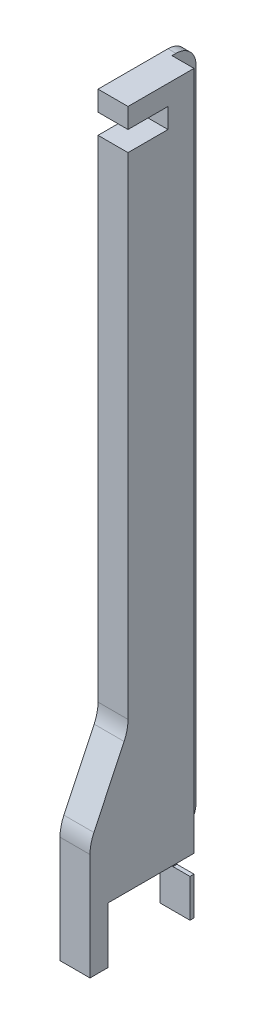
SolidWorks part; units mm, degrees
ref_plane "정면" through (0, 0, 0) normal (0, 0, 1) x (1, 0, 0)
ref_plane "윗면" through (0, 0, 0) normal (0, 1, 0) x (1, 0, 0)
ref_plane "우측면" through (0, 0, 0) normal (1, 0, 0) x (0, 0, -1)
sketch "스케치1" plane through (0, 0, 0) normal (0, 0, 1) x (1, 0, 0)
  line L0 (-318.5049, 0) -> (318.5049, 0) construction
  line L1 (0, 0) -> (0, -258.8265) construction
  line L2 (-168, 0) -> (168, 0)
  line L3 (-168, -20) -> (168, -20)
  line L4 (168, -20) -> (168, 0) construction
  line L5 (168, -20) -> (168, -340)
  line L6 (172, -340) -> (172, 0)
  line L7 (168, 0) -> (183, 0)
  line L8 (183, 0) -> (183, -340)
  line L9 (183, -340) -> (168, -340)
  line L10 (-168, -20) -> (-168, 0) construction
  line L11 (-183, -340) -> (-168, -340)
  line L12 (-183, 0) -> (-183, -340)
  line L13 (-168, 0) -> (-183, 0)
  line L14 (-172, -340) -> (-172, 0)
  line L15 (-168, -20) -> (-168, -340)
  line L16 (168, -20) -> (168, 0)
  line L17 (-168, -20) -> (-168, 0)
  point P14 (0, -20)
  dimension "D1" = 168
  dimension "D2" = 20
  dimension "D3" = 4
  dimension "D4" = 340
  dimension "D5" = 15
extrude "보스-돌출1" add sketch "스케치1" along normal blind 26 contours L3 L5 L9 L8 L7 L2 L13 L12 L11 L15
extrude "보스-돌출2" add sketch "스케치1<4>" against normal blind 19 contours L16 L5 L9 L6 L7 | L15 L17 L13 L14 L11 region at (-170, -170, 0) region at (170, -170, 0)
sketch "스케치1<4>" plane through (0, 0, 0) normal (0, 0, 1) x (1, 0, 0) same geometry as "스케치1"
fillet "필렛1" radius 10 4 edges at (-170, 0, -19) (170, 0, -19) (170, -340, -19) (-170, -340, -19)
sketch "스케치2" plane through (172, 0, 0) normal (1, 0, 0) x (0, 0, -1)
  line L0 (14, -340) -> (14, 0)
  line L1 (12, 0) -> (12, -340)
  line L4 (19, -330) -> (19, -10)
  line L5 (9, 0) -> (0, 0)
  line L6 (0, 0) -> (0, -340)
  line L7 (0, -340) -> (9, -340)
  line L8 (19, -330) -> (19, -10)
  line L9 (9, 0) -> (0, 0)
  line L10 (0, 0) -> (0, -340)
  line L11 (0, -340) -> (9, -340)
  arc A2 (19, -10) -> (9, 0) centre (9, -10) ccw
  arc A3 (9, -340) -> (19, -330) centre (9, -330) ccw
  arc A4 (19, -10) -> (9, 0) centre (9, -10) ccw
  arc A5 (9, -340) -> (19, -330) centre (9, -330) ccw
  dimension "D2" = 5
  dimension "D3" = 2
  dimension "D1" = 0
sketch "스케치3" plane through (168, 0, 0) normal (-1, 0, 0) x (0, 0, 1)
  line L0 (-12, 0) -> (-12, -340) construction
  line L1 (-14, -340) -> (-14, 0) construction
  line L2 (-12, 0) -> (-12, -340)
  line L3 (-14, -340) -> (-14, 0)
  line L4 (-19, -10) -> (-19, -330)
  line L5 (0, 0) -> (-9, 0)
  line L6 (0, -340) -> (0, 0)
  line L7 (-9, -340) -> (0, -340)
  line L8 (-19, -10) -> (-19, -330)
  line L9 (0, 0) -> (-9, 0)
  line L10 (0, -340) -> (0, 0)
  line L11 (-9, -340) -> (0, -340)
  arc A2 (-9, 0) -> (-19, -10) centre (-9, -10) ccw
  arc A3 (-19, -330) -> (-9, -340) centre (-9, -330) ccw
  arc A4 (-9, 0) -> (-19, -10) centre (-9, -10) ccw
  arc A5 (-19, -330) -> (-9, -340) centre (-9, -330) ccw
  dimension "D1" = 0
sketch "스케치5" plane through (0, 0, 0) normal (0, 1, 0) x (1, 0, 0)
  line L0 (-7, 0) -> (-7, -26)
  line L1 (7, 0) -> (7, -26)
  line L2 (-168, 0) -> (-168, -6)
  line L3 (-168, -6) -> (-7, -6)
  line L4 (7, -6) -> (168, -6)
  line L5 (168, -6) -> (168, 0)
  line L12 (-168, 0) -> (-168, 9)
  line L13 (-168, 9) -> (-172, 9)
  line L14 (-172, 9) -> (-172, 0)
  line L15 (-172, 0) -> (-183, 0)
  line L16 (-183, 0) -> (-183, -26)
  line L17 (-183, -26) -> (183, -26)
  line L18 (183, -26) -> (183, 0)
  line L19 (183, 0) -> (172, 0)
  line L20 (172, 0) -> (172, 9)
  line L21 (172, 9) -> (168, 9)
  line L22 (168, 9) -> (168, 0)
  line L23 (168, 0) -> (-168, 0)
  line L24 (-168, 0) -> (-168, 9)
  line L25 (-168, 9) -> (-172, 9)
  line L26 (-172, 9) -> (-172, 0)
  line L27 (-172, 0) -> (-183, 0)
  line L28 (-183, 0) -> (-183, -26)
  line L29 (-183, -26) -> (183, -26)
  line L30 (183, -26) -> (183, 0)
  line L31 (183, 0) -> (172, 0)
  line L32 (172, 0) -> (172, 9)
  line L33 (172, 9) -> (168, 9)
  line L34 (168, 9) -> (168, 0)
  line L35 (168, 0) -> (-168, 0)
  line M27 (168, 0) -> (-168, 0)
  dimension "D2" = 7
  dimension "D3" = 7
  dimension "D4" = 6
  dimension "D1" = 0
extrude "컷-돌출1" cut sketch "스케치5" against normal blind 52 contours L2 L3 L0 M27 | L4 L5 L1 M27 region at (-87.5, 0, 3) region at (87.5, 0, 3)
extrude "보스-돌출4" add sketch "스케치1<5>" against normal blind 7 contours L9 L8 L7 L6 | L11 L14 L13 L12 region at (-177.5, -170, 0) region at (177.5, -170, 0)
sketch "스케치1<5>" plane through (0, 0, 0) normal (0, 0, 1) x (1, 0, 0) same geometry as "스케치1"
sketch "스케치6" plane through (0, -340, 0) normal (0, -1, 0) x (1, 0, 0)
  line L0 (-172, -7) -> (-126.7636, -7) construction
  line L1 (-172, -7) -> (-168, -7)
  line L2 (-168, -7) -> (-168, -5)
  line L3 (-168, -5) -> (-174.5, -5)
  line L4 (-174.5, -5) -> (-174.5, -7)
  line L5 (-181.1, -7) -> (-181.1, -5)
  line L6 (-172, -7) -> (-172, -9)
  line L7 (-172, -9) -> (-168, -9)
  line L8 (-168, -9) -> (-168, 26)
  line L9 (-168, 26) -> (-183, 26)
  line L10 (-183, 26) -> (-183, -7)
  line L11 (-183, -7) -> (-172, -7)
  line L12 (-172, -7) -> (-172, -9)
  line L13 (-172, -9) -> (-168, -9)
  line L14 (-168, -9) -> (-168, 26)
  line L15 (-168, 26) -> (-183, 26)
  line L16 (-183, 26) -> (-183, -7)
  line L17 (-183, -7) -> (-172, -7)
  line L18 (-181.1, -5) -> (-183, -5)
  line L19 (-181.1, -5) -> (-174.5, -5)
  line L20 (-168, 26) -> (-168, 36)
  line L21 (-168, 36) -> (-183, 36)
  line L22 (-183, 36) -> (-183, 26)
  line L23 (-168, 36) -> (-168, 45)
  line L24 (-168, 45) -> (-183, 45)
  line L25 (-183, 45) -> (-183, 36)
  line M14 (-168, -9) -> (-168, 26)
  line M15 (-168, 26) -> (-183, 26)
  line M17 (-183, -7) -> (-172, -7)
  dimension "D2" = 6.5
  dimension "D3" = 2
  dimension "D4" = 6.6
  dimension "D5" = 41
  dimension "D6" = 9
  dimension "D1" = 0
extrude "보스-돌출5" add sketch "스케치6" along normal blind 28 contours L5 L18 L16 M17 | L19 L5 L4 M17 | L3 L4 L1 M17 M14 region at (-171.25, -340, -6) region at (-177.8, -340, -6) region at (-182.05, -340, -6)
extrude "컷-돌출2" cut sketch "스케치6<3>" along normal blind 5 contours L19 L5 L4 M17 region at (-177.8, -340, -6)
sketch "스케치6<3>" plane through (0, -340, 0) normal (0, -1, 0) x (1, 0, 0) same geometry as "스케치6"
fillet "필렛2" radius 20 1 edges at (-170, -340, -7)
extrude "보스-돌출6" add sketch "스케치6<4>" against normal blind 30 contours L21 L22 L20 M15 | L24 L25 L21 L23 region at (-175.5, -340, 31) region at (-175.5, -340, 40.5)
sketch "스케치6<4>" plane through (0, -340, 0) normal (0, -1, 0) x (1, 0, 0) same geometry as "스케치6"
extrude "보스-돌출7" add sketch "스케치6<5>" along normal blind 28 contours L24 L25 L21 L23 region at (-175.5, -340, 40.5)
sketch "스케치6<5>" plane through (0, -340, 0) normal (0, -1, 0) x (1, 0, 0) same geometry as "스케치6"
sketch "스케치9" plane through (-183, 0, 0) normal (-1, 0, 0) x (0, 0, 1)
  line L0 (45, -310) -> (26, -270)
  line L1 (26, 0) -> (26, -310) construction
  line L12 (26, 0) -> (-7, 0)
  line L13 (-7, 0) -> (-7, -368)
  line L14 (-7, -368) -> (-5, -368)
  line L15 (-5, -368) -> (-5, -340)
  line L16 (-5, -340) -> (36, -340)
  line L17 (36, -340) -> (36, -368)
  line L18 (36, -368) -> (45, -368)
  line L19 (45, -368) -> (45, -310)
  line L20 (45, -310) -> (26, -310)
  line L21 (26, -310) -> (26, 0)
  line L22 (26, 0) -> (-7, 0)
  line L23 (-7, 0) -> (-7, -368)
  line L24 (-7, -368) -> (-5, -368)
  line L25 (-5, -368) -> (-5, -340)
  line L26 (-5, -340) -> (36, -340)
  line L27 (36, -340) -> (36, -368)
  line L28 (36, -368) -> (45, -368)
  line L29 (45, -368) -> (45, -310)
  line L30 (45, -310) -> (26, -310)
  line L31 (26, -310) -> (26, 0)
  line M19 (45, -310) -> (26, -310)
  line M20 (26, -310) -> (26, 0)
  dimension "D2" = 40
  dimension "D1" = 0
extrude "보스-돌출8" add sketch "스케치9" against normal blind 15 contours L0 M19 M20 region at (-183, -296.6667, 32.3333)
fillet "필렛3" radius 20 2 edges at (-175.5, -270, 26) (-175.5, -310, 45)
mirror "대칭 복사2" about plane through (0, 0, 0) normal (1, 0, 0) of "보스-돌출5", "컷-돌출2", "필렛3", "보스-돌출6", "보스-돌출7", "보스-돌출8"
fillet "필렛4" radius 20 1 edges at (170, -340, -7)
sketch "스케치10" plane through (183, 0, 0) normal (1, 0, 0) x (0, 0, -1)
  line L0 (-27.9344, -274.0725) -> (-43.0656, -305.9275) construction
  line L1 (-45, -314.5086) -> (-45, -368) construction
  line L2 (-45, -368) -> (-36, -368) construction
  line L3 (-36, -368) -> (-36, -340) construction
  line L4 (-36, -340) -> (5, -340) construction
  line L5 (5, -340) -> (5, -368) construction
  line L6 (5, -368) -> (7, -368) construction
  line L7 (7, -368) -> (7, -354) construction
  line L8 (19, -330) -> (19, -10) construction
  line L9 (9, 0) -> (-6, 0) construction
  line L10 (-6, 0) -> (-6, -20) construction
  line L11 (-6, -20) -> (-26, -20) construction
  line L12 (-26, -20) -> (-26, -265.4914) construction
  line L13 (-27.9344, -274.0725) -> (-43.0656, -305.9275) construction
  line L14 (-45, -314.5086) -> (-45, -368) construction
  line L15 (-45, -368) -> (-36, -368) construction
  line L16 (-36, -368) -> (-36, -340) construction
  line L17 (-36, -340) -> (5, -340) construction
  line L18 (5, -340) -> (5, -368) construction
  line L19 (5, -368) -> (7, -368) construction
  line L20 (7, -368) -> (7, 0) construction
  line L21 (7, 0) -> (-26, 0) construction
  line L22 (-26, 0) -> (-26, -265.4914) construction
  line L23 (-27.9344, -274.0725) -> (-43.0656, -305.9275)
  line L24 (-45, -314.5086) -> (-45, -368)
  line L25 (-45, -368) -> (-36, -368)
  line L26 (-36, -368) -> (-36, -340)
  line L27 (-36, -340) -> (5, -340)
  line L28 (5, -340) -> (5, -368)
  line L29 (5, -368) -> (7, -368)
  line L30 (7, -368) -> (7, -354)
  line L31 (19, -330) -> (19, -10)
  line L32 (9, 0) -> (-6, 0)
  line L33 (-6, 0) -> (-6, -20)
  line L34 (-6, -20) -> (-26, -20)
  line L35 (-26, -20) -> (-26, -265.4914)
  line L36 (-27.9344, -274.0725) -> (-43.0656, -305.9275)
  line L37 (-45, -314.5086) -> (-45, -368)
  line L38 (-45, -368) -> (-36, -368)
  line L39 (-36, -368) -> (-36, -340)
  line L40 (-36, -340) -> (5, -340)
  line L41 (5, -340) -> (5, -368)
  line L42 (5, -368) -> (7, -368)
  line L43 (7, -368) -> (7, 0)
  line L44 (7, 0) -> (-26, 0)
  line L45 (-26, 0) -> (-26, -265.4914)
  line L46 (-26, -10) -> (-6, -10)
  arc A0 (-43.0656, -305.9275) -> (-45, -314.5086) centre (-25, -314.5086) ccw construction
  arc A1 (15, -338) -> (7, -354) centre (27, -354) ccw construction
  arc A2 (15, -338) -> (19, -330) centre (9, -330) ccw construction
  arc A3 (19, -10) -> (9, 0) centre (9, -10) ccw construction
  arc A4 (-27.9344, -274.0725) -> (-26, -265.4914) centre (-46, -265.4914) ccw construction
  arc A5 (-43.0656, -305.9275) -> (-45, -314.5086) centre (-25, -314.5086) ccw construction
  arc A6 (-27.9344, -274.0725) -> (-26, -265.4914) centre (-46, -265.4914) ccw construction
  arc A7 (-43.0656, -305.9275) -> (-45, -314.5086) centre (-25, -314.5086) ccw
  arc A8 (15, -338) -> (7, -354) centre (27, -354) ccw
  arc A9 (15, -338) -> (19, -330) centre (9, -330) ccw
  arc A10 (19, -10) -> (9, 0) centre (9, -10) ccw
  arc A11 (-27.9344, -274.0725) -> (-26, -265.4914) centre (-46, -265.4914) ccw
  arc A12 (-43.0656, -305.9275) -> (-45, -314.5086) centre (-25, -314.5086) ccw
  arc A13 (-27.9344, -274.0725) -> (-26, -265.4914) centre (-46, -265.4914) ccw
sketch "스케치11" plane through (168, 0, 0) normal (-1, 0, 0) x (0, 0, 1)
  line L10 (43.0656, -305.9275) -> (27.9344, -274.0725)
  line L11 (45, -368) -> (45, -314.5086)
  line L12 (36, -368) -> (45, -368)
  line L13 (45, -368) -> (45, -314.5086)
  line L14 (43.0656, -305.9275) -> (27.9344, -274.0725)
  line L15 (26, -265.4914) -> (26, -20)
  line L16 (26, -20) -> (6, -20)
  line L17 (6, -20) -> (6, 0)
  line L18 (6, 0) -> (-9, 0)
  line L19 (-19, -10) -> (-19, -330)
  line L20 (-7, -354) -> (-7, -368)
  line L21 (-7, -368) -> (-5, -368)
  line L22 (-5, -368) -> (-5, -340)
  line L23 (-5, -340) -> (36, -340)
  line L24 (36, -340) -> (36, -368)
  line L25 (36, -368) -> (45, -368)
  line L26 (45, -368) -> (45, -314.5086)
  line L27 (43.0656, -305.9275) -> (27.9344, -274.0725)
  line L28 (26, -265.4914) -> (26, -20)
  line L29 (26, -20) -> (6, -20)
  line L30 (6, -20) -> (6, 0)
  line L31 (6, 0) -> (-9, 0)
  line L32 (-19, -10) -> (-19, -330)
  line L33 (-7, -354) -> (-7, -368)
  line L34 (-7, -368) -> (-5, -368)
  line L35 (-5, -368) -> (-5, -340)
  line L36 (-5, -340) -> (36, -340)
  line L37 (36, -340) -> (36, -368)
  line L38 (36, -368) -> (45, -368)
  line L39 (36, -340) -> (36, -368)
  line L40 (-5, -340) -> (36, -340)
  line L41 (-5, -368) -> (-5, -340)
  line L42 (-7, -368) -> (-5, -368)
  line L43 (-7, 0) -> (-7, -368)
  line L44 (26, 0) -> (-7, 0)
  line L45 (26, -265.4914) -> (26, 0)
  line L46 (43.0656, -305.9275) -> (27.9344, -274.0725)
  line L47 (45, -368) -> (45, -314.5086)
  line L48 (36, -368) -> (45, -368)
  line L49 (36, -340) -> (36, -368)
  line L50 (-5, -340) -> (36, -340)
  line L51 (-5, -368) -> (-5, -340)
  line L52 (-7, -368) -> (-5, -368)
  line L53 (-7, 0) -> (-7, -368)
  line L54 (26, 0) -> (-7, 0)
  line L55 (26, -265.4914) -> (26, 0)
  arc A2 (45, -314.5086) -> (43.0656, -305.9275) centre (25, -314.5086) ccw
  arc A3 (26, -265.4914) -> (27.9344, -274.0725) centre (46, -265.4914) ccw
  arc A4 (45, -314.5086) -> (43.0656, -305.9275) centre (25, -314.5086) ccw
  arc A5 (45, -314.5086) -> (43.0656, -305.9275) centre (25, -314.5086) ccw
  arc A6 (26, -265.4914) -> (27.9344, -274.0725) centre (46, -265.4914) ccw
  arc A7 (-9, 0) -> (-19, -10) centre (-9, -10) ccw
  arc A8 (-19, -330) -> (-15, -338) centre (-9, -330) ccw
  arc A9 (-7, -354) -> (-15, -338) centre (-27, -354) ccw
  arc A10 (45, -314.5086) -> (43.0656, -305.9275) centre (25, -314.5086) ccw
  arc A11 (26, -265.4914) -> (27.9344, -274.0725) centre (46, -265.4914) ccw
  arc A12 (-9, 0) -> (-19, -10) centre (-9, -10) ccw
  arc A13 (-19, -330) -> (-15, -338) centre (-9, -330) ccw
  arc A14 (-7, -354) -> (-15, -338) centre (-27, -354) ccw
  arc A15 (26, -265.4914) -> (27.9344, -274.0725) centre (46, -265.4914) ccw
  line M31 (45, -368) -> (45, -314.5086)
  arc M32 (45, -314.5086) -> (43.0656, -305.9275) centre (25, -314.5086) ccw
  line M33 (43.0656, -305.9275) -> (27.9344, -274.0725)
  arc M34 (27.9344, -274.0725) -> (26, -265.4914) centre (46, -265.4914) cw
  line M35 (26, -265.4914) -> (26, -20)
  line M36 (26, -20) -> (6, -20)
  line M37 (6, -20) -> (6, 0)
  line M38 (6, 0) -> (-9, 0)
  arc M39 (-9, 0) -> (-19, -10) centre (-9, -10) ccw
  line M40 (-19, -10) -> (-19, -330)
  arc M41 (-19, -330) -> (-15, -338) centre (-9, -330) ccw
  arc M42 (-15, -338) -> (-7, -354) centre (-27, -354) cw
  line M43 (-7, -354) -> (-7, -368)
  line M44 (-7, -368) -> (-5, -368)
  line M45 (-5, -368) -> (-5, -340)
  line M46 (-5, -340) -> (36, -340)
  line M47 (36, -340) -> (36, -368)
  line M48 (36, -368) -> (45, -368)
  dimension "D1" = 0
  dimension "D2" = 0
extrude "컷-돌출3" cut sketch "스케치11" along normal blind 617 contours L53 M38 M43 M44 M45 M46 M47 M48 M31 M32 M33 M34 M35 M36 M37 | L55 L54 M36 M37 | L53 L31 M39 M40 M41 M42 region at (168, -191.2863, 11.8028) region at (168, -10, 16) region at (168, -171.1237, -12.9334)
extrude "컷-돌출4" cut sketch "스케치10" against normal blind 617 contours L46 L45 L34 L33 region at (183, -15, 16)
sketch "스케치12" plane through (168, 0, 0) normal (-1, 0, 0) x (0, 0, 1)
  line L0 (18, -203) -> (18, -163)
  line L1 (18, -163) -> (10, -163)
  line L2 (10, -163) -> (10, -203)
  line L3 (10, -203) -> (-19, -203)
  line L4 (18.2, -203) -> (18.2, -162.8)
  line L5 (18.2, -162.8) -> (9.8, -162.8)
  line L6 (9.8, -162.8) -> (9.8, -203)
  line L15 (26, -183) -> (-19, -183) construction
  line L16 (26, -203) -> (18, -203)
  line L18 (-7, 0) -> (-9, 0)
  line L19 (-7, -354) -> (-7, 0)
  line L20 (-19, -10) -> (-19, -330)
  line L21 (-7, 0) -> (-9, 0)
  line L22 (-7, -354) -> (-7, 0)
  line L23 (-19, -10) -> (-19, -330)
  line L30 (6, -10) -> (26, -10)
  line L31 (26, -10) -> (26, 0)
  line L32 (26, 0) -> (-9, 0)
  line L33 (-19, -10) -> (-19, -330)
  line L34 (-7, -354) -> (-7, -368)
  line L35 (-7, -368) -> (-5, -368)
  line L36 (-5, -368) -> (-5, -340)
  line L37 (-5, -340) -> (36, -340)
  line L38 (36, -340) -> (36, -368)
  line L39 (36, -368) -> (45, -368)
  line L40 (45, -368) -> (45, -314.5086)
  line L41 (43.0656, -305.9275) -> (27.9344, -274.0725)
  line L42 (26, -265.4914) -> (26, -20)
  line L43 (26, -20) -> (6, -20)
  line L44 (6, -20) -> (6, -10)
  line L45 (6, -10) -> (26, -10)
  line L46 (26, -10) -> (26, 0)
  line L47 (26, 0) -> (-9, 0)
  line L48 (-19, -10) -> (-19, -330)
  line L49 (-7, -354) -> (-7, -368)
  line L50 (-7, -368) -> (-5, -368)
  line L51 (-5, -368) -> (-5, -340)
  line L52 (-5, -340) -> (36, -340)
  line L53 (36, -340) -> (36, -368)
  line L54 (36, -368) -> (45, -368)
  line L55 (45, -368) -> (45, -314.5086)
  line L56 (43.0656, -305.9275) -> (27.9344, -274.0725)
  line L57 (26, -265.4914) -> (26, -20)
  line L58 (26, -20) -> (6, -20)
  line L59 (6, -20) -> (6, -10)
  arc A8 (-7, -354) -> (-15, -338) centre (-27, -354) ccw
  arc A9 (-19, -330) -> (-15, -338) centre (-9, -330) ccw
  arc A10 (-9, 0) -> (-19, -10) centre (-9, -10) ccw
  arc A11 (-19, -330) -> (-15, -338) centre (-9, -330) ccw
  arc A12 (-7, -354) -> (-15, -338) centre (-27, -354) ccw
  arc A13 (45, -314.5086) -> (43.0656, -305.9275) centre (25, -314.5086) ccw
  arc A14 (26, -265.4914) -> (27.9344, -274.0725) centre (46, -265.4914) ccw
  arc A15 (-9, 0) -> (-19, -10) centre (-9, -10) ccw
  arc A16 (-19, -330) -> (-15, -338) centre (-9, -330) ccw
  arc A17 (-7, -354) -> (-15, -338) centre (-27, -354) ccw
  arc A18 (45, -314.5086) -> (43.0656, -305.9275) centre (25, -314.5086) ccw
  arc A19 (26, -265.4914) -> (27.9344, -274.0725) centre (46, -265.4914) ccw
  arc A20 (-9, 0) -> (-19, -10) centre (-9, -10) ccw
  arc A21 (-7, -354) -> (-15, -338) centre (-27, -354) ccw
  arc A22 (-19, -330) -> (-15, -338) centre (-9, -330) ccw
  arc A23 (-9, 0) -> (-19, -10) centre (-9, -10) ccw
  dimension "D3" = 185
  dimension "D4" = 8
  dimension "D5" = 8
  dimension "D6" = 20
  dimension "D7" = 20
  dimension "D1" = 0
  dimension "D2" = 0
  dimension "D8" = 0.2
sketch "스케치13" plane through (183, 0, 0) normal (1, 0, 0) x (0, 0, -1)
  line L0 (5, -340) -> (7, -340)
  line L1 (7, 0) -> (7, -368) construction
  line L2 (7, -340) -> (7, -349)
  line L3 (7, -349) -> (5, -349)
  line L4 (5, -368) -> (5, -340) construction
  line L5 (5, -349) -> (5, -340)
  dimension "D1" = 9
extrude "컷-돌출7" cut sketch "스케치13" against normal blind 8.5
